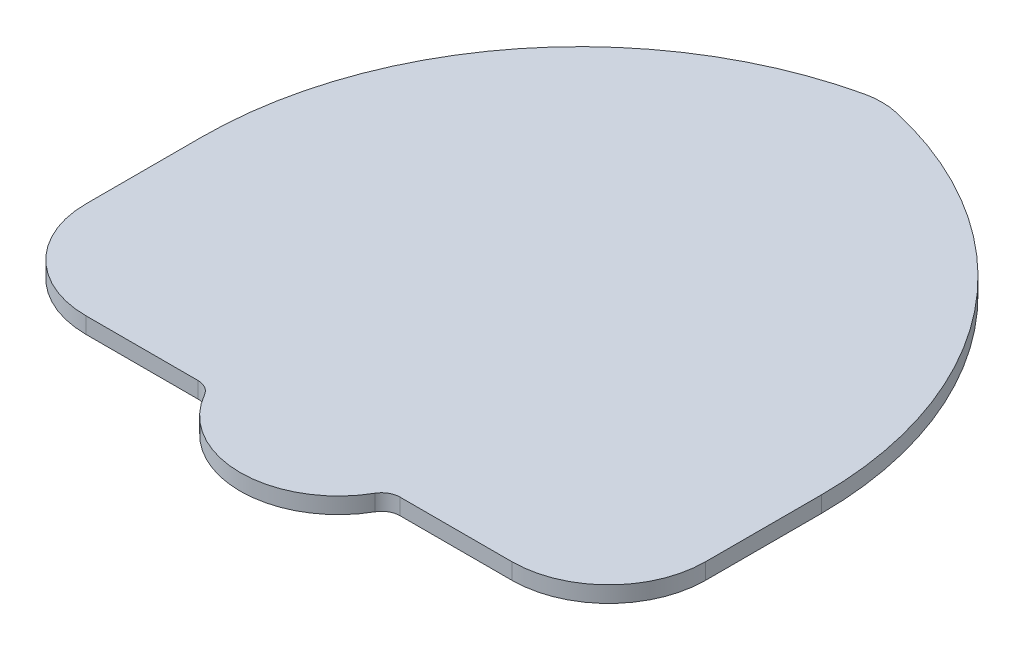
SolidWorks part; units mm, degrees
material "Body Cover"
ref_plane "Front Plane" through (0, 0, 0) normal (0, 0, 1) x (1, 0, 0)
ref_plane "Top Plane" through (0, 0, 0) normal (0, 1, 0) x (1, 0, 0)
ref_plane "Right Plane" through (0, 0, 0) normal (1, 0, 0) x (0, 0, -1)
sketch "Sketch1" plane through (0, 0, 0) normal (0, 1, 0) x (1, 0, 0)
  line L0 (107.315, 0) -> (107.315, 379.476) construction
  line L1 (0, 0) -> (214.63, 0)
  line L2 (0, 0) -> (0, 73.66)
  line L3 (214.63, 0) -> (214.63, 73.66)
  arc A0 (107.315, 202.438) -> (214.63, 73.66) centre (83.7057, 73.66) cw
  arc A2 (107.315, 202.438) -> (0, 73.66) centre (130.9243, 73.66) ccw
  dimension "D1" = 214.63
  dimension "D3" = 202.438
  dimension "D4" = 73.66
extrude "Boss-Extrude1" add sketch "Sketch1" along normal blind 5.588
fillet "Fillet1" radius 25.4 1 edges at (107.315, 2.794, -202.438)
sketch "Sketch2" plane through (0, 5.588, 0) normal (0, 1, 0) x (1, 0, 0)
  line L0 (0, 0) -> (214.63, 0) construction
  line L1 (107.315, 0) -> (107.315, -103.6479) construction
  line L2 (107.315, -20.32) -> (335.0178, -20.32) construction
  line L3 (73.3326, 13.6624) -> (73.3326, 0)
  line L4 (141.2974, 13.6624) -> (141.2974, 0)
  arc A0 (76.2, 0) -> (138.43, 0) centre (107.315, 13.6624) ccw
  line M5 (0, 0) -> (214.63, 0)
  dimension "D1" = 76.2
  dimension "D2" = 20.32
extrude "Boss-Extrude2" add sketch "Sketch2" against normal up to surface (5.588 mm away) contours A0 M5 | A0 L3 M5 | A0 L4 M5 region at (107.315, 5.588, 8.3806) up to face at (107.315, 0, -97.6703)
fillet "Fillet2" radius 6.35 2 edges at (138.43, 2.794, 0) (76.2, 2.794, 0)
fillet "Fillet3" radius 33.528 2 edges at (214.63, 2.794, 0) (0, 2.794, 0)
